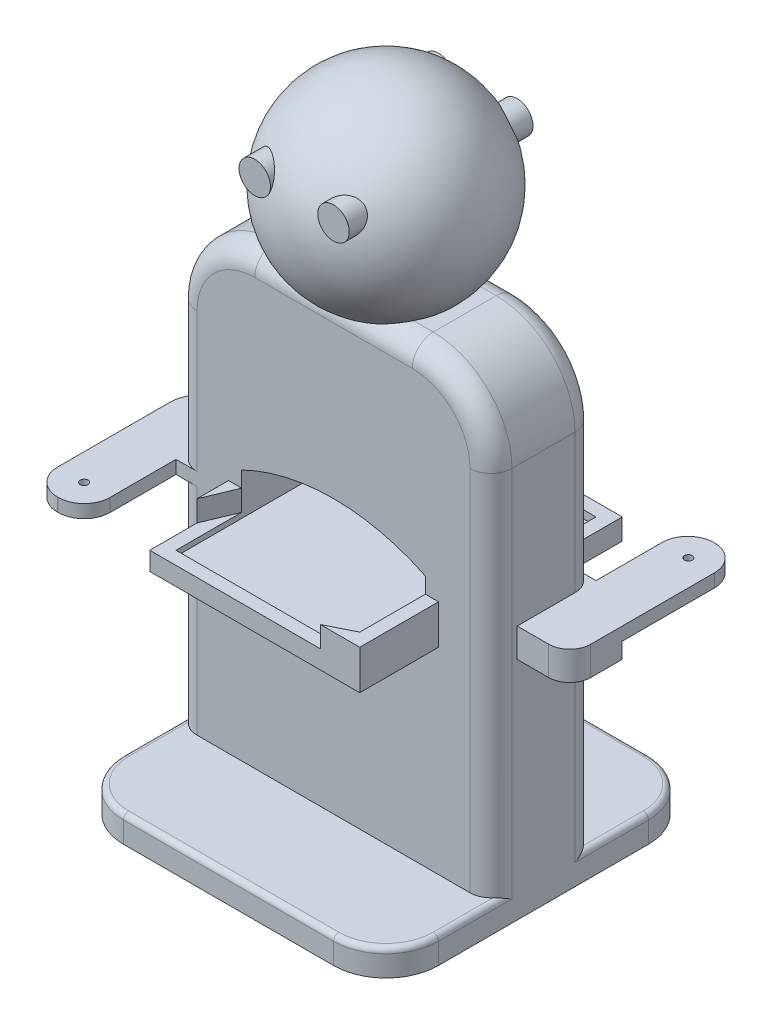
SolidWorks part; units mm, degrees
ref_plane "Front Plane" through (0, 0, 0) normal (0, 0, 1) x (1, 0, 0)
ref_plane "Top Plane" through (0, 0, 0) normal (0, 1, 0) x (1, 0, 0)
ref_plane "Right Plane" through (0, 0, 0) normal (1, 0, 0) x (0, 0, -1)
sketch "Sketch1" plane through (0, 0, 0) normal (0, 0, 1) x (1, 0, 0)
  line L1 (-30, 85) -> (30, 85)
  line L2 (-60, 55) -> (-60, -85)
  line L3 (-60, -85) -> (60, -85)
  line L4 (60, 55) -> (60, -85)
  line L5 (-60, 85) -> (60, -85) construction
  line L6 (-60, -85) -> (60, 85) construction
  arc A0 (30, 85) -> (60, 55) centre (30, 55) cw
  arc A1 (-30, 85) -> (-60, 55) centre (-30, 55) ccw
  point P0 (0, 0)
  dimension "D3" = 30
  dimension "D1" = 120
  dimension "D2" = 170
extrude "Boss-Extrude1" add sketch "Sketch1" along normal blind 20
sketch "Sketch2" plane through (0, 0, 0) normal (0, 0, 1) x (1, 0, 0)
  line L1 (0, 75) -> (0, 150) construction
  line L2 (0, 75) -> (0, 150)
  line L3 (30, 85) -> (-30, 85) construction
  arc A0 (0, 75) -> (0, 150) centre (0, 112.5) ccw
  dimension "D1" = 75
  dimension "D2" = 10
revolve "Revolve1" add sketch "Sketch2" angle 360 about L1
sketch "Sketch3" plane through (0, 0, 20) normal (0, 0, 1) x (1, 0, 0)
  line L1 (-35, 5) -> (35, 5)
  line L2 (-35, 5) -> (-35, -5)
  line L3 (-35, -5) -> (35, -5)
  line L4 (35, 5) -> (35, -5)
  line L5 (-35, 5) -> (35, -5) construction
  line L6 (-35, -5) -> (35, 5) construction
  point P0 (0, 0)
  dimension "D1" = 70
  dimension "D2" = 10
extrude "Cut-Extrude1" cut sketch "Sketch3" against normal blind 30
sketch "Sketch4" plane through (0, 0, 20) normal (0, 0, 1) x (1, 0, 0)
  line L8 (-35, 5) -> (-35, -5) construction
  line L9 (-35, -5) -> (35, -5) construction
  line L13 (40, -10) -> (40, 5)
  line L14 (-40, 5) -> (-40, -10)
  line L15 (-40, -10) -> (40, -10)
  line L16 (35, -5) -> (35, 5)
  line L17 (-35, 5) -> (-35, -5)
  line L18 (-35, -5) -> (35, -5)
  line L19 (-35, 5) -> (-40, 5)
  line L20 (35, 5) -> (40, 5)
  dimension "D1" = 15
  dimension "D2" = 5
  dimension "D3" = 5
  dimension "D4" = 10
  dimension "D5" = 70
  dimension "D6" = 70
extrude "Boss-Extrude2" add sketch "Sketch4" along normal blind 25
sketch "Sketch5" plane through (0, 0, 45) normal (0, 0, 1) x (1, 0, 0)
  line L1 (-40, 5) -> (40, 5)
  line L2 (-40, 5) -> (-40, -10)
  line L3 (-40, -10) -> (40, -10)
  line L4 (40, 5) -> (40, -10)
extrude "Boss-Extrude3" add sketch "Sketch5" along normal blind 5
sketch "Sketch7" plane through (0, -85, 0) normal (0, -1, 0) x (1, 0, 0)
  line L1 (-40, 60) -> (40, 60)
  line L2 (-60, 40) -> (-60, -40)
  line L3 (-40, -60) -> (40, -60)
  line L4 (60, 40) -> (60, -40)
  line L5 (-60, 60) -> (60, -60) construction
  line L6 (-60, -60) -> (60, 60) construction
  arc A0 (40, 60) -> (60, 40) centre (40, 40) cw
  arc A1 (-60, -40) -> (-40, -60) centre (-40, -40) ccw
  arc A2 (40, -60) -> (60, -40) centre (40, -40) ccw
  arc A3 (-40, 60) -> (-60, 40) centre (-40, 40) ccw
  point P0 (0, 0)
  dimension "D3" = 20
  dimension "D1" = 120
  dimension "D2" = 120
extrude "Boss-Extrude4" add sketch "Sketch7" along normal blind 10
sketch "Sketch8" plane through (0, 5, 0) normal (0, 1, 0) x (1, 0, 0)
  line L0 (-40, -32) -> (-35, -20)
  line L1 (35, -45) -> (25, -50)
  line L2 (-60, -20) -> (-30, -20) construction
  line L10 (35, -45) -> (-35, -45)
  line L11 (-35, -45) -> (-35, -20)
  line L12 (-35, -20) -> (-40, -20)
  line L13 (-35, -20) -> (-40, -20)
  line L14 (-40, -20) -> (-40, -50)
  line L15 (-40, -50) -> (40, -50)
  line L16 (40, -50) -> (40, -20)
  line L17 (40, -20) -> (35, -20)
  line L18 (40, -20) -> (35, -20)
  line L19 (35, -20) -> (35, -45)
  line L20 (35, -45) -> (-35, -45)
  line L21 (-35, -45) -> (-35, -20)
  line L24 (-40, -32) -> (-40, -50)
  line L25 (-40, -50) -> (25, -50)
  line M13 (35, -45) -> (-35, -45)
  line M14 (-35, -45) -> (-35, -20)
  line M17 (-40, -20) -> (-40, -50)
  line M18 (-40, -50) -> (40, -50)
  dimension "D2" = 12
  dimension "D3" = 15
  dimension "D1" = 0
sketch "Sketch9" plane through (-60, 0, 0) normal (-1, 0, 0) x (0, 0, 1)
  line L1 (-10, -3) -> (10, -3)
  line L2 (-10, -3) -> (-10, -9)
  line L3 (-10, -9) -> (10, -9)
  line L4 (10, -3) -> (10, -9)
  line L5 (-10, -3) -> (10, -9) construction
  line L6 (-10, -9) -> (10, -3) construction
  point P0 (0, -6)
  dimension "D1" = 6
  dimension "D2" = 6
  dimension "D3" = 20
extrude "Boss-Extrude5" add sketch "Sketch9" along normal blind 20
fillet "Fillet1" radius 12.5 1 edges at (-80, -6, -10)
sketch "Sketch11" plane through (0, -3, 0) normal (0, 1, 0) x (1, 0, 0)
  line L0 (-80, -10) -> (-80, -45.1)
  line L1 (-70.1, -55) -> (-69.9, -55)
  line L2 (-60, -45.1) -> (-60, 10)
  line L3 (-67.5, 10) -> (-60, 10) construction
  line L4 (-60, 10) -> (-67.5, 10)
  line L5 (-80, -2.5) -> (-80, -10)
  line L6 (-80, -10) -> (-60, -10)
  line L7 (-60, -10) -> (-60, 0)
  line L8 (-60, 10) -> (-67.5, 10)
  line L9 (-80, -2.5) -> (-80, -10)
  line L10 (-80, -10) -> (-60, -10)
  line L11 (-60, -10) -> (-60, 0)
  line L17 (-60, 0) -> (-60, 10)
  line L19 (-60, 0) -> (-60, 10)
  arc A0 (-80, -45.1) -> (-70.1, -55) centre (-70.1, -45.1) ccw
  arc A1 (-67.5, 10) -> (-80, -2.5) centre (-67.5, -2.5) ccw
  arc A2 (-67.5, 10) -> (-80, -2.5) centre (-67.5, -2.5) ccw
  arc A3 (-69.9, -55) -> (-60, -45.1) centre (-69.9, -45.1) ccw
  point P11 (-80, -55)
  point P14 (-60, -55)
  line M6 (-60, 10) -> (-67.5, 10)
  arc M7 (-67.5, 10) -> (-80, -2.5) centre (-67.5, -2.5) ccw
  line M8 (-80, -2.5) -> (-80, -10)
  line M9 (-80, -10) -> (-60, -10)
  dimension "D4" = 9.9
  dimension "D5" = 9.9
  dimension "D2" = 20
  dimension "D3" = 65
  dimension "D1" = 0
extrude "Cut-Extrude4" cut sketch "Sketch8" against normal blind 8 contours L1 L0 M13 M14 M17 M18 region at (-36.7544, 5, 26.3107)
extrude "Boss-Extrude6" add sketch "Sketch11" along normal blind 5 contours L1 A3 L2 L0 A0 M9 | L2 M9 M6 M7 M8 region at (-70, -3, 31.5052) region at (-69.3405, -3, 0.6595)
mirror "Mirror2" about plane through (-30, 55, 0) normal (0, 0, 1) of "Boss-Extrude3", "Boss-Extrude2", "Cut-Extrude1", "Boss-Extrude1"
sketch "Sketch12" plane through (0, 5, 0) normal (0, 1, 0) x (1, 0, 0)
  line L0 (35, 20) -> (40, 32)
  line L1 (-35, 45) -> (-25, 50)
  line L8 (35, 20) -> (40, 20)
  line L9 (40, 20) -> (40, 50)
  line L10 (40, 50) -> (-40, 50)
  line L11 (-40, 50) -> (-40, 20)
  line L12 (-40, 20) -> (-35, 20)
  line L13 (-35, 20) -> (-35, 45)
  line L14 (-35, 45) -> (35, 45)
  line L15 (35, 45) -> (35, 20)
  line L17 (40, 32) -> (40, 50)
  line L18 (40, 50) -> (-25, 50)
  line L22 (-35, 45) -> (35, 45)
  line L23 (35, 45) -> (35, 20)
  dimension "D2" = 15
  dimension "D3" = 12
  dimension "D1" = 0
extrude "Cut-Extrude5" cut sketch "Sketch12" against normal blind 7
mirror "Mirror3" about plane through (0, 0, 0) normal (1, 0, 0) of "Boss-Extrude5"
fillet "Fillet2" radius 8 1 edges at (80, -6, 10)
sketch "Sketch13" plane through (0, -3, 0) normal (0, 1, 0) x (1, 0, 0)
  line L0 (80, 10) -> (80, 45.1)
  line L1 (70.1, 55) -> (69.9, 55)
  line L2 (60, 45.1) -> (60, -10)
  line L4 (60, -10) -> (72, -10)
  line L5 (80, -2) -> (80, 10)
  line L6 (80, 10) -> (60, 10)
  line L7 (60, 10) -> (60, -10)
  line L8 (60, -10) -> (72, -10)
  line L9 (80, -2) -> (80, 10)
  line L10 (80, 10) -> (60, 10)
  arc A0 (80, 45.1) -> (70.1, 55) centre (70.1, 45.1) ccw
  arc A1 (72, -10) -> (80, -2) centre (72, -2) ccw
  arc A2 (72, -10) -> (80, -2) centre (72, -2) ccw
  arc A3 (69.9, 55) -> (60, 45.1) centre (69.9, 45.1) ccw
  point P11 (80, 55)
  point P14 (60, 55)
  line M8 (60, -10) -> (72, -10)
  arc M9 (72, -10) -> (80, -2) centre (72, -2) ccw
  line M10 (80, -2) -> (80, 10)
  line M11 (80, 10) -> (60, 10)
  dimension "D4" = 9.9
  dimension "D2" = 20
  dimension "D3" = 65
  dimension "D1" = 0
extrude "Boss-Extrude7" add sketch "Sketch13" along normal blind 5 contours L2 M11 M8 M9 M10 | L1 A3 L2 L0 A0 M11 region at (70, -3, -31.5052) region at (69.708, -3, -0.292)
sketch "Sketch14" plane through (0, 0, -20) normal (0, 0, -1) x (-1, 0, 0)
  line L0 (-35, 5) -> (-35, 11)
  line L1 (35, 11) -> (35, 5)
  line L2 (35, 5) -> (40, 5) construction
  line L3 (25, 5) -> (40, 5) construction
  line L4 (-35, 5) -> (35, 5) construction
  line L6 (40, 5) -> (40, -10) construction
  line L7 (35, 5) -> (-35, 5)
  arc A0 (-35, 11) -> (35, 11) centre (0, -60.9375) cw
  dimension "D2" = 80
  dimension "D1" = 5
  dimension "D3" = 6
extrude "Cut-Extrude6" cut sketch "Sketch14" against normal blind 15
mirror "Mirror5" about plane through (0, 0, 0) normal (0, 0, 1) of "Cut-Extrude6"
sketch "Sketch15" plane through (0, 2, 0) normal (0, 1, 0) x (1, 0, 0)
  circle A0 centre (70.1, 45.1) radius 1.5
  circle A1 centre (-69.9, -45.1) radius 1.5
  dimension "D1" = 3
  dimension "D2" = 3
extrude "Cut-Extrude7" cut sketch "Sketch15" against normal through all
sketch "Sketch16" plane through (0, 0, 0) normal (0, 0, 1) x (1, 0, 0)
  line L0 (-15, 125) -> (15, 125) construction
  circle A0 centre (-15, 125) radius 6
  circle A1 centre (15, 125) radius 6
  point P4 (0, 125)
  dimension "D1" = 12
  dimension "D2" = 30
  dimension "D3" = 125
extrude "Boss-Extrude8" add sketch "Sketch16" along normal mid plane 70
sketch "Sketch17" plane through (0, -95, 0) normal (0, -1, 0) x (1, 0, 0)
  line L0 (-40, 50) -> (-40, 30) construction
  line L1 (-40, 50) -> (-40, 30)
  arc A0 (-40, 30) -> (-40, 50) centre (-40, 40) ccw
  dimension "D1" = 20
revolve "Revolve2" add sketch "Sketch17" angle 360 about L0
mirror "Mirror6" about plane through (0, 0, 0) normal (0, 0, 1) of "Revolve2"
mirror "Mirror7" about plane through (0, 0, 0) normal (1, 0, 0) of "Mirror6"
fillet "Fillet3" radius 8 12 edges at (60, 28.5, -20) (-22.9057, 85, -20) (-51.2132, 76.2132, -20) (60, -15, 20) (-22.9057, 85, 20) (-51.2132, 76.2132, 20) (60, -44, -20) (51.2132, 76.2132, -20) (-60, -15, -20) (-60, -44, 20) (51.2132, 76.2132, 20) (-60, 28.5, 20)
fillet "Fillet4" radius 2 10 edges at (60, -85, -26) (54.1421, -85, -54.1421) (0, -85, -60) (-54.1421, -85, -54.1421) (60, -85, 26) (54.1421, -85, 54.1421) (0, -85, 60) (-60, -85, 26) (-60, -85, -26) (-54.1421, -85, 54.1421)
